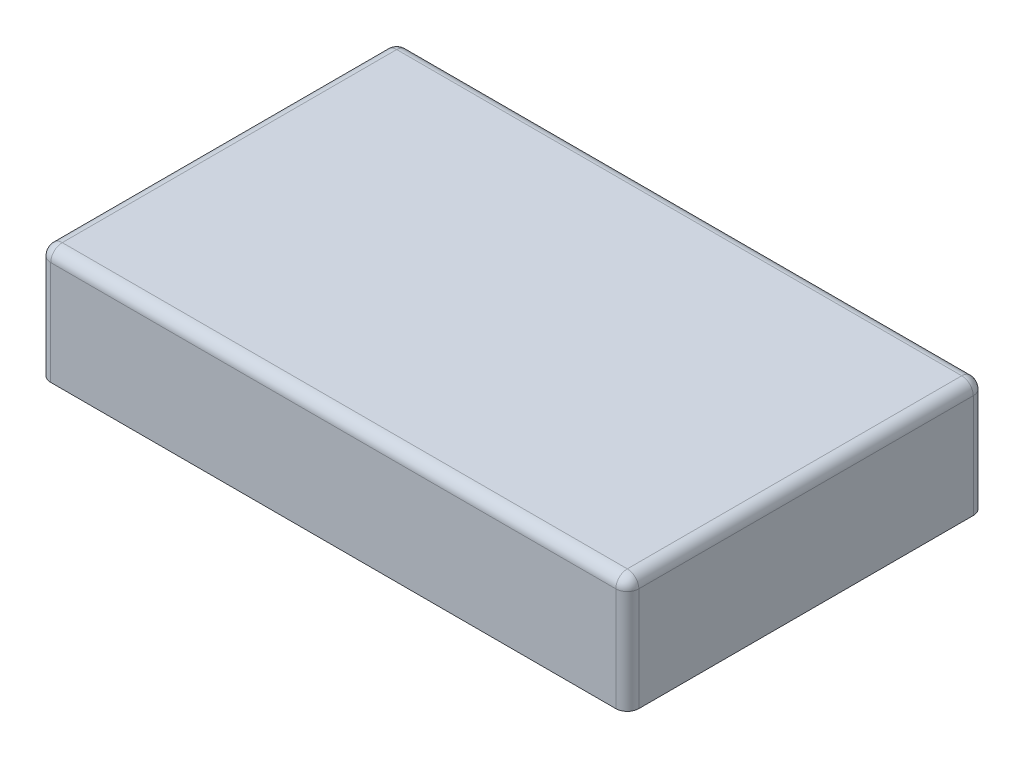
SolidWorks part; units mm, degrees
ref_plane "Front Plane" through (0, 0, 0) normal (0, 0, 1) x (1, 0, 0)
ref_plane "Top Plane" through (0, 0, 0) normal (0, 1, 0) x (1, 0, 0)
ref_plane "Right Plane" through (0, 0, 0) normal (1, 0, 0) x (0, 0, -1)
sketch "Sketch1" plane through (0, 0, 0) normal (0, 1, 0) x (1, 0, 0)
  line L1 (-49, -31) -> (49, -31)
  line L2 (-51, -29) -> (-51, 29)
  line L3 (-49, 31) -> (49, 31)
  line L4 (51, -29) -> (51, 29)
  line L5 (-51, -31) -> (51, 31) construction
  line L6 (-51, 31) -> (51, -31) construction
  arc A0 (49, -31) -> (51, -29) centre (49, -29) ccw
  arc A1 (49, 31) -> (51, 29) centre (49, 29) cw
  arc A2 (-49, -31) -> (-51, -29) centre (-49, -29) cw
  arc A3 (-51, 29) -> (-49, 31) centre (-49, 29) cw
  point P0 (0, 0)
  dimension "D3" = 2
  dimension "D1" = 102
  dimension "D2" = 62
extrude "Boss-Extrude1" add sketch "Sketch1" along normal blind 20
fillet "Fillet1" radius 2 8 edges at (0, 20, 31) (-50.4142, 20, 30.4142) (-51, 20, 0) (-50.4142, 20, -30.4142) (0, 20, -31) (50.4142, 20, -30.4142) (51, 20, 0) (50.4142, 20, 30.4142)
shell "Shell1" thickness 2 removed face at (0, 0, 0)
fillet "Fillet2" radius 1 12 edges at (0, 0, 29) (0, 0, -29) (0, 18, 29) (0, 18, -29) (-49, 18, 0) (-49, 9, -29) (-49, 0, 0) (-49, 9, 29) (49, 18, 0) (49, 9, 29) (49, 0, 0) (49, 9, -29)
